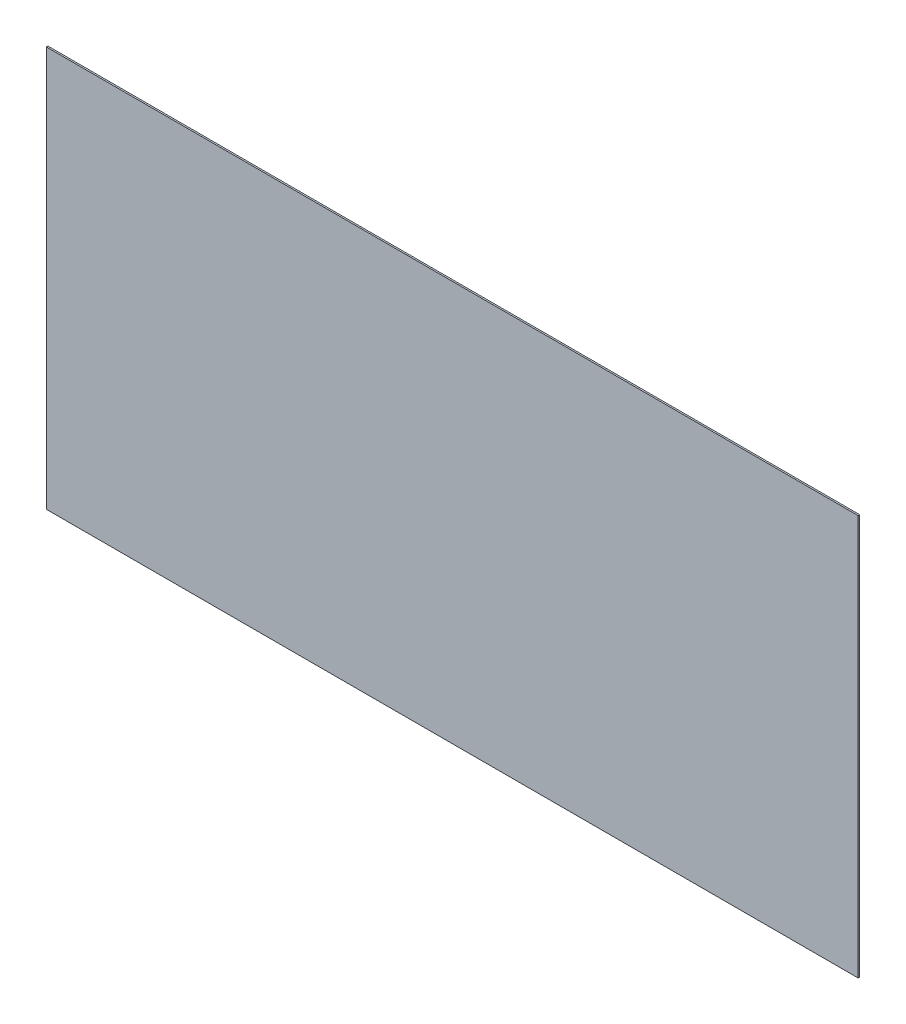
SolidWorks part; units mm, degrees
material "Oak"
ref_plane "Front Plane" through (0, 0, 0) normal (0, 0, 1) x (1, 0, 0)
ref_plane "Top Plane" through (0, 0, 0) normal (0, 1, 0) x (1, 0, 0)
ref_plane "Right Plane" through (0, 0, 0) normal (1, 0, 0) x (0, 0, -1)
sketch "Sketch1" plane through (0, 0, 0) normal (0, 0, 1) x (1, 0, 0)
  line L0 (0, 0) -> (259.5, 0)
  line L1 (259.5, 0) -> (259.5, 128)
  line L2 (259.5, 128) -> (0, 128)
  line L3 (0, 128) -> (0, 0)
extrude "Boss-Extrude1" add sketch "Sketch1" along normal blind 0.5
